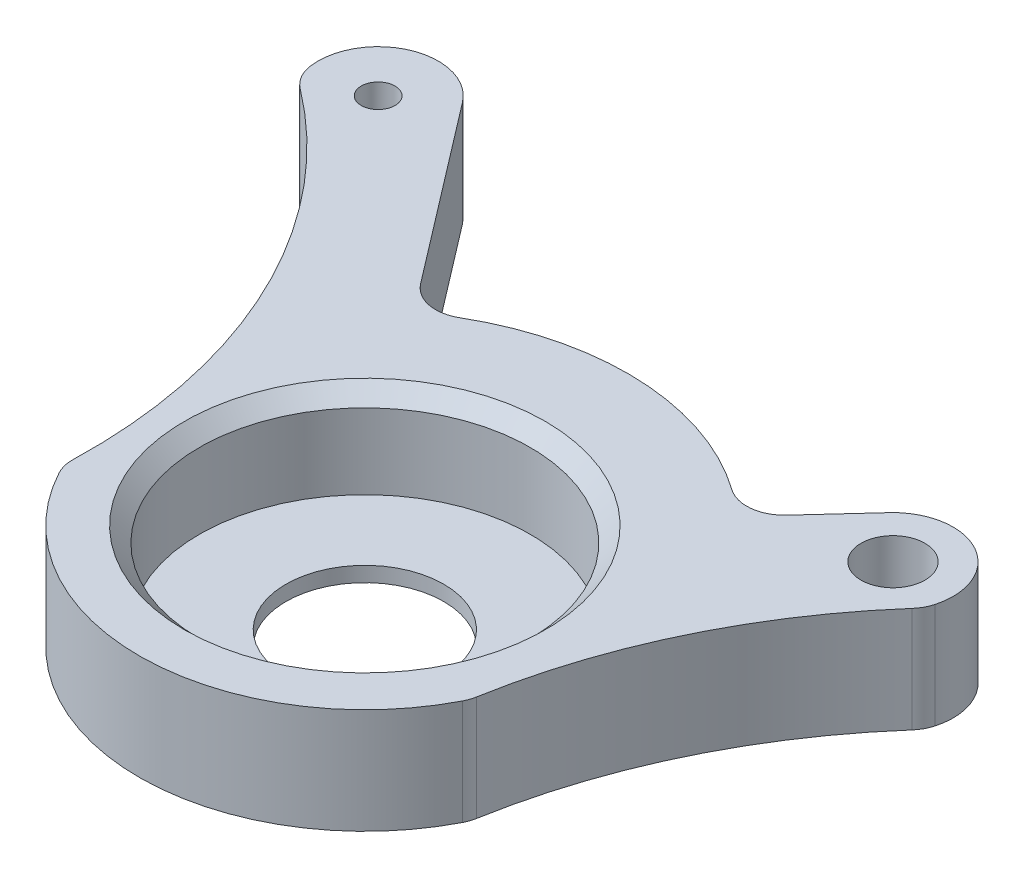
SolidWorks part; units mm, degrees
ref_plane "Front Plane" through (0, 0, 0) normal (0, 0, 1) x (1, 0, 0)
ref_plane "Top Plane" through (0, 0, 0) normal (0, 1, 0) x (1, 0, 0)
ref_plane "Right Plane" through (0, 0, 0) normal (1, 0, 0) x (0, 0, -1)
sketch "Sketch1" plane through (0, 0, 0) normal (0, 1, 0) x (1, 0, 0)
  line L0 (-13.5208, -6.4952) -> (-27.9083, 23.4548)
  line L1 (-23.4393, 29.0926) -> (20.4998, 19.3787)
  line L2 (23.2419, 13.741) -> (13.5208, -6.4952)
  line L3 (-24.3027, 25.1869) -> (0, 0) construction
  line L4 (0, 0) -> (19.6363, 15.473) construction
  line L5 (19.6363, 15.473) -> (-24.3027, 25.1869) construction
  circle A0 centre (0, 0) radius 11
  arc A1 (-13.5208, -6.4952) -> (13.5208, -6.4952) centre (0, 0) ccw
  arc A2 (20.4998, 19.3787) -> (23.2419, 13.741) centre (19.6363, 15.473) cw
  arc A3 (-27.9083, 23.4548) -> (-23.4393, 29.0926) centre (-24.3027, 25.1869) cw
  circle A4 centre (-24.3027, 25.1869) radius 1.125
  circle A5 centre (19.6363, 15.473) radius 2.125
  dimension "D1" = 22
  dimension "D2" = 15
  dimension "D3" = 4
  dimension "D4" = 35
  dimension "D6" = 2.25
  dimension "D8" = 4.25
  dimension "D5" = 45
  dimension "D7" = 25
extrude "Boss-Extrude1" add sketch "Sketch1" along normal blind 6
sketch "Sketch3" plane through (0, 6, 0) normal (0, 1, 0) x (1, 0, 0)
  line L0 (16.6899, 18.1782) -> (11.8354, 12.8908)
  line L1 (20.4998, 19.3787) -> (-23.4393, 29.0926) construction
  line L2 (20.4998, 19.3787) -> (-23.4393, 29.0926)
  line L5 (-21.1256, 27.6171) -> (-10.6325, 13.8996)
  circle A0 centre (0, 0) radius 17.5 construction
  circle A1 centre (-24.3027, 25.1869) radius 4 construction
  circle A2 centre (19.6363, 15.473) radius 4 construction
  arc A3 (-23.4393, 29.0926) -> (-21.1256, 27.6171) centre (-24.3027, 25.1869) cw
  arc A4 (16.6899, 18.1782) -> (20.4998, 19.3787) centre (19.6363, 15.473) cw
  arc A5 (-10.6325, 13.8996) -> (11.8354, 12.8908) centre (0, 0) cw
  line M5 (20.4998, 19.3787) -> (-23.4393, 29.0926)
  dimension "D1" = 35
  dimension "D2" = 8
  dimension "D3" = 8
chamfer "Chamfer1" distance 1 angle 45 1 edges at (0, 6, 11)
extrude "Cut-Extrude2" cut sketch "Sketch3" against normal through all contours L5 A5 L0 A4 A3 M5 region at (-2.592, 6, -20.6025)
sketch "Sketch5" plane through (0, 6, 0) normal (0, 1, 0) x (1, 0, 0)
  line L1 (-27.9083, 23.4548) -> (-13.5208, -6.4952) construction
  line L2 (-27.9083, 23.4548) -> (-13.5208, -6.4952)
  line L4 (13.5208, -6.4952) -> (23.2419, 13.741) construction
  line L5 (13.5208, -6.4952) -> (23.2419, 13.741)
  arc A0 (-27.9083, 23.4548) -> (-13.5208, -6.4952) centre (-48.4826, -4.8594) cw
  arc A1 (23.2419, 13.741) -> (13.5208, -6.4952) centre (52.9881, -13.0016) ccw
  dimension "D1" = 35
  dimension "D2" = 40
extrude "Cut-Extrude3" cut sketch "Sketch5" against normal through all
fillet "Fillet2" radius 2.5 6 edges at (11.8354, 3, -12.8908) (-10.6325, 3, -13.8996) (-13.5208, 3, 6.4952) (-27.9083, 3, -23.4548) (13.5208, 3, 6.4952) (23.2419, 3, -13.741)
sketch "Sketch4" plane through (0, 0, 0) normal (0, -1, 0) x (1, 0, 0)
  line L4 (-21.1256, -27.6171) -> (-12.0561, -15.7607)
  line L5 (13.4201, -14.6168) -> (16.6899, -18.1782)
  line L8 (-21.1256, -27.6171) -> (-12.0561, -15.7607)
  line L9 (13.4201, -14.6168) -> (16.6899, -18.1782)
  circle A0 centre (19.6363, -15.473) radius 2.125 construction
  circle A1 centre (-24.3027, -25.1869) radius 1.125 construction
  circle A2 centre (19.6363, -15.473) radius 2.125
  circle A3 centre (-24.3027, -25.1869) radius 1.125
  circle A4 centre (0, 0) radius 5.25
  arc A6 (-28.27, -24.6765) -> (-21.1256, -27.6171) centre (-24.3027, -25.1869) ccw
  arc A7 (-8.8116, -15.1197) -> (-12.0561, -15.7607) centre (-10.0704, -17.2796) ccw
  arc A8 (-8.8116, -15.1197) -> (10.1312, -14.2692) centre (0, 0) ccw
  arc A9 (13.4201, -14.6168) -> (10.1312, -14.2692) centre (11.5785, -16.3076) ccw
  arc A10 (16.6899, -18.1782) -> (23.4928, -14.4112) centre (19.6363, -15.473) ccw
  arc A11 (13.3411, 6.8567) -> (-13.1978, 7.1287) centre (0, 0) ccw
  arc A12 (-28.27, -24.6765) -> (-21.1256, -27.6171) centre (-24.3027, -25.1869) ccw
  arc A13 (-8.8116, -15.1197) -> (-12.0561, -15.7607) centre (-10.0704, -17.2796) ccw
  arc A14 (-8.8116, -15.1197) -> (10.1312, -14.2692) centre (0, 0) ccw
  arc A15 (13.4201, -14.6168) -> (10.1312, -14.2692) centre (11.5785, -16.3076) ccw
  arc A16 (16.6899, -18.1782) -> (23.4928, -14.4112) centre (19.6363, -15.473) ccw
  arc A17 (13.3411, 6.8567) -> (-13.1978, 7.1287) centre (0, 0) ccw
  arc A24 (-27.3033, -23.0052) -> (-13.4971, 5.8685) centre (-48.4826, 4.8594) ccw
  arc A25 (-27.3033, -23.0052) -> (-13.4971, 5.8685) centre (-48.4826, 4.8594) ccw
  arc A28 (-13.1978, 7.1287) -> (-13.4971, 5.8685) centre (-10.9982, 5.9406) ccw
  arc A29 (-13.1978, 7.1287) -> (-13.4971, 5.8685) centre (-10.9982, 5.9406) ccw
  arc A30 (-27.3033, -23.0052) -> (-28.27, -24.6765) centre (-25.7905, -24.9955) ccw
  arc A31 (-27.3033, -23.0052) -> (-28.27, -24.6765) centre (-25.7905, -24.9955) ccw
  arc A33 (13.5806, 6.1426) -> (22.9593, -13.4233) centre (52.9881, 13.0016) ccw
  arc A34 (13.5806, 6.1426) -> (22.9593, -13.4233) centre (52.9881, 13.0016) ccw
  arc A37 (13.5806, 6.1426) -> (13.3411, 6.8567) centre (11.1176, 5.7139) ccw
  arc A38 (13.5806, 6.1426) -> (13.3411, 6.8567) centre (11.1176, 5.7139) ccw
  arc A39 (23.4928, -14.4112) -> (22.9593, -13.4233) centre (21.0825, -15.0748) ccw
  arc A40 (23.4928, -14.4112) -> (22.9593, -13.4233) centre (21.0825, -15.0748) ccw
  dimension "D2" = 10.5
  dimension "D1" = 0
extrude "Boss-Extrude2" add sketch "Sketch4" along normal blind 1
